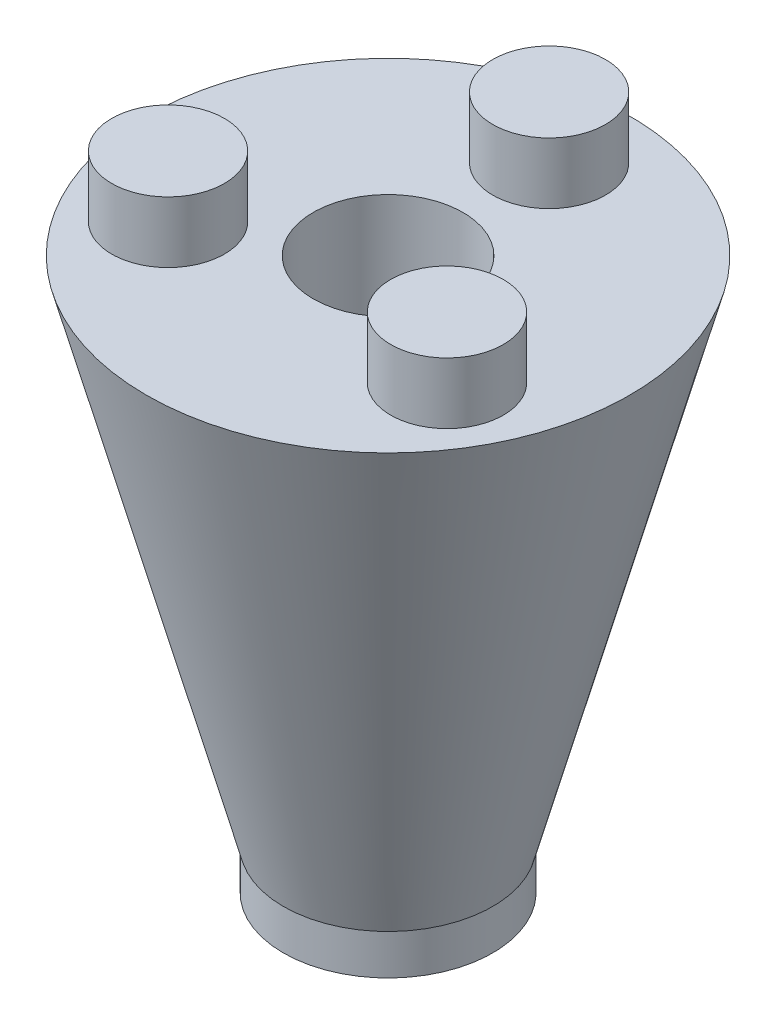
SolidWorks part; units mm, degrees
material "Polyester Resin"
ref_plane "Front Plane" through (0, 0, 0) normal (0, 0, 1) x (1, 0, 0)
ref_plane "Top Plane" through (0, 0, 0) normal (0, 1, 0) x (1, 0, 0)
ref_plane "Right Plane" through (0, 0, 0) normal (1, 0, 0) x (0, 0, -1)
sketch "Sketch1" plane through (0, 0, 0) normal (0, 1, 0) x (1, 0, 0)
  circle A0 centre (0, 0) radius 6.5
  circle A6 centre (0, 0) radius 6.5
  dimension "D7" = 13
extrude "AngleBody" add sketch "Sketch1" along normal blind 31.75 draft 15 contours A0 region at (0, 0, 0) draft outward yes
sketch "Sketch2" plane through (0, 31.75, 0) normal (0, 1, 0) x (1, 0, 0)
  line L0 (-8.6603, -5) -> (8.6603, -5)
  line L1 (8.6603, -5) -> (0, 10)
  line L2 (0, 10) -> (-8.6603, -5)
  circle A0 centre (0, 0) radius 4.65
  circle A1 centre (0, 0) radius 1.935
  circle A2 centre (0, 10) radius 3.5
  circle A3 centre (8.6603, -5) radius 3.5
  circle A4 centre (-8.6603, -5) radius 3.5
  dimension "D1" = 9.3
  dimension "D2" = 3.87
  dimension "D5" = 7
  dimension "D3" = 10
  dimension "D4" = 10
extrude "CenterHole" cut sketch "Sketch2" against normal through all contours A1 | A0 A1 region at (-4.5185, 31.75, 0) region at (0, 31.75, 0)
extrude "40tPegs" add sketch "Sketch2<3>" along normal blind 3.8 contours L1 A2 L2 | L2 A2 L1 | L0 A4 L2 | L2 A4 L0 | L1 A3 L0 | L0 A3 L1 region at (-6.7306, 31.75, 3.8859) region at (-9.0462, 31.75, 5.2228) region at (6.7306, 31.75, 3.8859) region at (9.0462, 31.75, 5.2228) region at (0, 31.75, -10.4456) region at (0, 31.75, -7.7718)
sketch "Sketch2<3>" plane through (0, 31.75, 0) normal (0, 1, 0) x (1, 0, 0) same geometry as "Sketch2"
sketch "Sketch3" plane through (0, 0, 0) normal (0, -1, 0) x (1, 0, 0)
  circle A0 centre (0, 0) radius 6.5 construction
  circle A2 centre (0, 0) radius 6.5
  circle A3 centre (0, 0) radius 3.3
  dimension "D1" = 6.6
extrude "20tInterface" add sketch "Sketch3" along normal blind 2.5
equation "\"CageLeftBottomEdge\"=22.11mm"
equation "\"CageLeftTopEdge\"=22.11mm"
equation "\"CageRightBottomEdge\"=21.63mm"
equation "\"CageRightTopEdge\"=21.63mm"
equation "\"CageHeight\"=86.04mm"
equation "\"CageLength\"=73.76mm"
equation "\"CageTopScrewClearance\"=10mm"
equation "\"CageBottomScrewClearance\"=25mm"
equation "\"CageLeftTopDepth\"= 11.65mm"
equation "\"CageLeftBottomDepth\"=11.11mm"
equation "\"CageLeftTopHeight\"=8.56175mm"
equation "\"CageLeftBottomHeight\"=16mm"
equation "\"CageRightTopDepth\"= 11.05mm"
equation "\"CageRightBottomDepth\"=10.58mm"
equation "\"CageRightTopHeight\"=9.6mm"
equation "\"CageRightBottomHeight\"=15.49mm"
equation "\"CageLeftTopChannelDepth\"=2.41908mm"
equation "\"CageLeftBottomChannelDepth\"=2.588mm"
equation "\"CageLeftChannelHeight\"=11.7mm"
equation "\"CageRightTopChannelDepth\"=2.32mm"
equation "\"CageRightBottomChannelDepth\"=2.318mm"
equation "\"CageRightChannelHeight\"=10mm"
equation "\"CageChanRelHeight\"=23.99mm"
equation "\"CageChanRelDepth\"=5.492mm"
equation "\"CageChamberRadius\"=16.261mm"
equation "\"CageScrewDiameter\"=4.8mm"
equation "\"CageSetScrewDiameter\"=3.5mm"
equation "\"CageAxleRadius\"=6.639mm"
equation "\"CageAxleKeyHeight\"=1.619mm"
equation "\"CageAxleKeyWidth\"=2.662mm"
equation "\"CageHoseWindowWidth\"=16.29mm"
equation "\"CageHoseWindowHeight\"=26.5mm"
equation "\"CageHoseWindow-Edge\"=8.89mm"
equation "\"CageScrew-VerticalEdge\"=5.0mm"
equation "\"CageScrew-HorizontalEdge\"=7.5mm"
equation "\"CageScrew-HoseCornerScrewEdge\"=4.45mm"
equation "\"CageAxle-BottomEdge\"=56.05mm"
equation "\"CageAxle-FrontEdge\"=46.03mm"
equation "\"CageBackSetScrew-Axle\"=40mm"
equation "\"CageFrontSetScrew-Axle\"=22mm"
equation "\"CageVelocityWindow-BackEdge\"=34.8mm"
equation "\"CageVelocityWindow-BottomEdge\"=27.55mm"
equation "\"CageVelocityWindowHeight\"=22.29mm"
equation "\"CageVelocityWindowWidth\"=12.61mm"
equation "\"TriggerSlot-BottomEdge\"=6.35mm"
equation "\"TriggerSlot-FrontEdge\"=15mm"
equation "\"TriggerSlotSize\"=6.7mm"
equation "\"TriggerRackOffset\"=.236224in"
equation "\"TriggerSlotSizeInt\"=.25in"
equation "\"MotorMountLegLength\"=.25in"
equation "\"GearOffset\"=.264907in"
equation "\"TriggerSlotSpacing\"=.25in"
equation "\"TriggerMiniSlotWidth\"=3.5mm"
equation "\"TriggerRackWidth\"=6.5mm"
equation "\"whitemotordepth\"=11.27mm"
equation "\"whitemotorbackdepth\"=3.845mm"
equation "\"whitemotoraxledepth\" = 3.5mm"
equation "\"whitemotoraxleoffset\"=11.4mm"
equation "\"whitemotorwidth\"=12.07mm"
equation "\"whitemotorheight\"=16.68mm"
equation "\"whitemotorcylinderlength\" =13.04mm"
equation "\"whitemotorcylinderradius\"=3.845mm"
equation "\"whitemotorcylinderoffset\"=2.35mm"
equation "\"whitemotorcutoutlength\"=1.88mm"
equation "\"whitemotorouterrad\"=5mm"
equation "\"whitemotorinnerrad\"=2.95mm"
equation "\"elasticracklength\"=2in"
equation "\"elasticrackpegsize\"=.25in"
equation "\"elasticrackpegbuffer\"=.125in"
equation "\"elasticrackpegspacing\"=1.76476378in"
equation "\"elasticbaybuffer\"=.25in"
equation "\"elasticdepth\"=.125in"
equation "\"elasticbaydepth\"=.75in"
equation "\"motormountwidth\"=12mm"
equation "\"motormountcornerfillet\"=3mm"
equation "\"pandiscradius\"=14in"
equation "\"towermaterialwidth\"=.25in"
equation "\"towerslotlength\"=.5in"
equation "\"towermarkerspace\"=5in"
equation "\"towerslothorizoffset\"=1in"
equation "\"towerslothorizspacing\"=2in"
equation "\"towerslotvertoffset\"=3in"
equation "\"towerslotvertspacing\"=1in"
equation "\"towerheight\"=12in"
equation "\"towerupslot\"=1in"
equation "\"toweraxle\"=.5in"
equation "\"stepperouterrad\"=10mm"
equation "\"stepperscrewsize\"=3.45mm"
equation "\"stepperscrewc2c\"=49.5mm"
equation "\"stepperdepthoffset\"=24mm"
equation "\"stepperhorizoffset\"=22.91mm"
equation "\"shaftslotOD\"=18.8mm"
equation "\"shaftslotID\"=13.28mm"
equation "\"shaftkeywidth\"=2.67mm"
equation "\"shaftkeydepth\"=1.8mm"
equation "\"shaftcollartotaldepth\"=12.5mm"
equation "\"shaftsquaredepth\"=6mm"
equation "\"shaftsetscrewsize\"=3.5mm"
equation "\"shaftkeytightdepth\"=1.85mm"
equation "\"shaftslottightID\"=12.78mm"
equation "\"shaftsetscrewoffset\"=9mm"
equation "\"cagecollartotaldepth\"=10mm"
equation "\"cagecollartotalwidth\"=35mm"
equation "\"cagecollarbasedepth\"=4mm"
equation "\"ajaxaxlesize\"=3.87mm"
equation "\"ajax4020gap\"=29.5mm"
equation "\"ajax4010gap\"=24.5mm"
equation "\"shortconangle\"=20deg"
equation "\"longconangle\"=15deg"
equation "\"D3@AngleBody\"=\"longconangle\""
equation "\"shortconlen\"=.875in"
equation "\"longconlen\"=1.25in"
equation "\"D1@AngleBody\"=\"longconlen\""
equation "\"D1@CenterHole\"=\"ajaxhubdepth\"+.1in"
equation "\"D2@Sketch2\"=\"ajaxaxlesize\""
equation "\"ajax40hubholeoffset\"=10mm"
equation "\"D3@Sketch2\"=\"ajax40hubholeoffset\""
equation "\"D4@Sketch2\"=\"ajax40hubholeoffset\""
equation "\"ajax40hubholesize\"=7.21mm"
equation "\"D5@Sketch2\"=\"ajax40hubholesize\"-.21mm"
equation "\"ajaxwidth\"=6.1mm"
equation "\"ajaxcutoutdepth\"=2.3mm"
equation "\"D1@40tPegs\"=\"ajaxwidth\"-\"ajaxcutoutdepth\""
equation "\"ajax20cutoutint\"=13.4mm"
equation "\"D7@Sketch1\"=\"ajax20cutoutint\"-.4mm"
equation "\"ajax40hubbuffer\"=8.9mm"
equation "\"D1@Sketch2\"=\"ajax40hubbuffer\"+.4mm"
equation "\"ajax20hubbuffer\"=6.1mm"
equation "\"D1@Sketch3\"=\"ajax20hubbuffer\"+.5mm"
equation "\"D1@20tInterface\"=\"ajaxcutoutdepth\"+.2mm"
equation "\"gearhubintdiam\"=30mm"
equation "\"gearhubintwid\"=15mm"
equation "\"towerspeedwidth\"=2in"
equation "\"towerspeedheight\"=8in"
equation "\"towerspeedgap\"=2in"
equation "\"stepperaxleflat\"=.037in"
equation "\"stepperaxlerad\"=0.11811024in"
equation "\"ajaxinnercut\"=2.3mm"
equation "\"ajaxdiametral\"=25.8854"
equation "\"ajax20hubholeoffset\"=.19685in"
equation "\"ajax20hubholesize\"=.059055in"
equation "\"ajax40cutoutint\"=32.6mm"
equation "\"bearingpandiscrad\"=6.8in"
equation "\"bearingpandiscang\"=48.75deg"
equation "\"bearingclearholedist\"=4.7345in"
equation "\"bearingclearholesize\"=.5in"
equation "\"bearingclearholeang\"=22.5deg"
equation "\"bearingmountholedist\"=4.25in"
equation "\"bearingwirehole\"=1.5in"
equation "\"no6diam\"=.146in"
